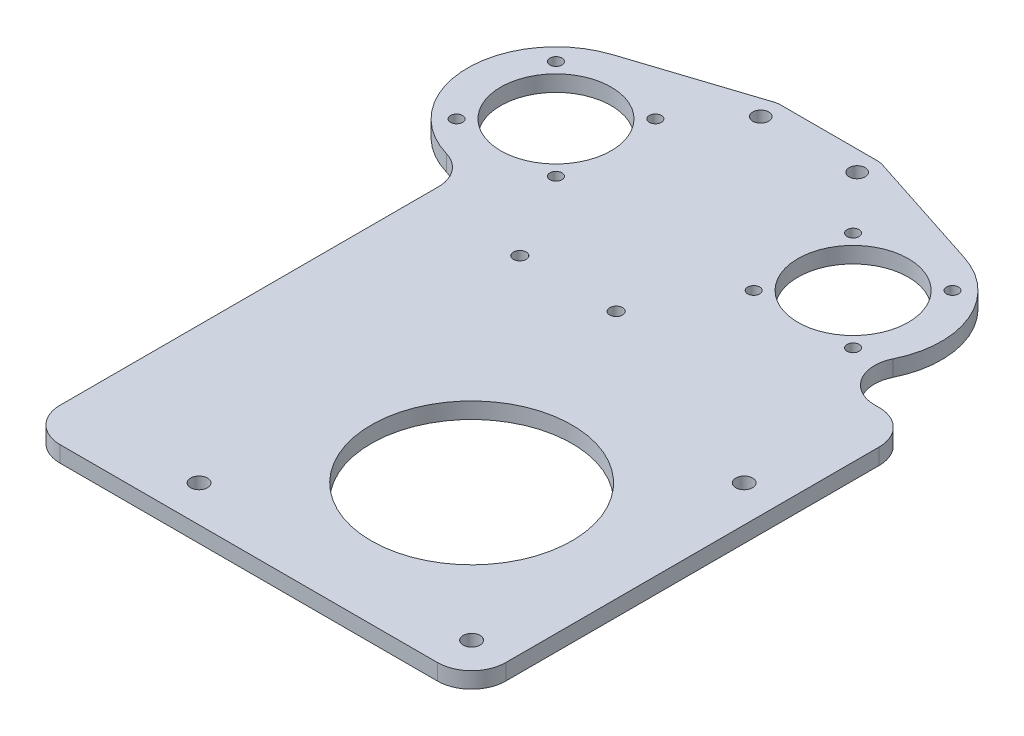
SolidWorks part; units mm, degrees
material "Thornel Mat VMA"
ref_plane "前视基准面" through (0, 0, 0) normal (0, 0, 1) x (1, 0, 0)
ref_plane "上视基准面" through (0, 0, 0) normal (0, 1, 0) x (1, 0, 0)
ref_plane "右视基准面" through (0, 0, 0) normal (1, 0, 0) x (0, 0, -1)
sketch "草图1" plane through (0, 0, 0) normal (0, 1, 0) x (1, 0, 0)
  line L0 (-37, 0) -> (37, 0) construction
  line L1 (-12, 4) -> (12, 4) construction
  line L2 (-12, 4) -> (-12, 26) construction
  line L3 (-12, 26) -> (12, 26) construction
  line L4 (12, 4) -> (12, 26) construction
  line L5 (-12, 4) -> (12, 26) construction
  line L6 (-12, 26) -> (12, 4) construction
  line L7 (37, 0) -> (49.3744, 12.3744) construction
  line L8 (0, 0) -> (0, 24.025) construction
  line L9 (-43.7997, 20.9228) -> (-13.5454, 30.7552)
  line L10 (-12, 31) -> (12, 31)
  line L11 (13.5454, 30.7552) -> (43.7997, 20.9228)
  line L12 (-37, -22) -> (37, -22)
  circle A0 centre (-12, 26) radius 2
  circle A1 centre (12, 26) radius 2
  circle A2 centre (12, 4) radius 2 construction
  circle A3 centre (-12, 4) radius 2 construction
  circle A5 centre (37, 0) radius 17.5 construction
  circle A6 centre (49.3744, 12.3744) radius 1.5
  circle A7 centre (49.3744, -12.3744) radius 1.5
  circle A8 centre (24.6256, -12.3744) radius 1.5
  circle A9 centre (24.6256, 12.3744) radius 1.5
  circle A10 centre (-49.3744, -12.3744) radius 1.5
  circle A11 centre (-24.6256, -12.3744) radius 1.5
  circle A12 centre (-49.3744, 12.3744) radius 1.5
  circle A13 centre (-24.6256, 12.3744) radius 1.5
  arc A14 (-43.7997, 20.9228) -> (-37, -22) centre (-37, 0) ccw
  arc A15 (-12, 31) -> (-13.5454, 30.7552) centre (-12, 26) ccw
  arc A16 (13.5454, 30.7552) -> (12, 31) centre (12, 26) ccw
  arc A17 (43.7997, 20.9228) -> (37, -22) centre (37, 0) cw
  circle A18 centre (-37, 0) radius 13.75
  circle A19 centre (37, 0) radius 13.75
  point P0 (0, 15)
  point P23 (37, 0)
  dimension "D4" = 4
  dimension "D6" = 35
  dimension "D7" = 45
  dimension "D8" = 3
  dimension "D10" = 44
  dimension "D11" = 10
  dimension "D12" = 27.5
  dimension "D2" = 24
  dimension "D3" = 22
  dimension "D5" = 74
  dimension "D13" = 26
  dimension "D9" = 4
extrude "凸台-拉伸1" add sketch "草图1" along normal blind 4
sketch "Sketch1" plane through (0, 4, 0) normal (0, 1, 0) x (1, 0, 0)
  line L0 (-37, -22) -> (37, -22) construction
  line L1 (-37, -22) -> (74, -22)
  line L2 (-37, -22) -> (-37, -132)
  line L3 (-37, -132) -> (74, -132)
  line L4 (74, -22) -> (74, -132)
  arc A2 (-12, -89) -> (31, -46) centre (31, -89) ccw construction
  circle A3 centre (12, -34) radius 1.6 construction
  circle A4 centre (-12, -34) radius 1.6 construction
  circle A5 centre (-2.9411, -122.9411) radius 2.1 construction
  circle A6 centre (64.9411, -122.9411) radius 2.1 construction
  circle A7 centre (64.9411, -55.0589) radius 2.1 construction
  circle A8 centre (12, -34) radius 1.6
  circle A9 centre (-12, -34) radius 1.6
  circle A10 centre (-2.9411, -122.9411) radius 2.1
  circle A11 centre (64.9411, -122.9411) radius 2.1
  circle A12 centre (64.9411, -55.0589) radius 2.1
  circle A13 centre (31, -89) radius 25
  dimension "D1" = 50
extrude "Boss-Extrude1" add sketch "Sketch1" against normal up to vertex (4 mm away) up to point (-37, 0, 22)
fillet "Fillet1" radius 8.5 5 edges at (74, 2, 22) (74, 2, 132) (-37, 2, 132) (37, 2, 22) (-37, 2, 22)
